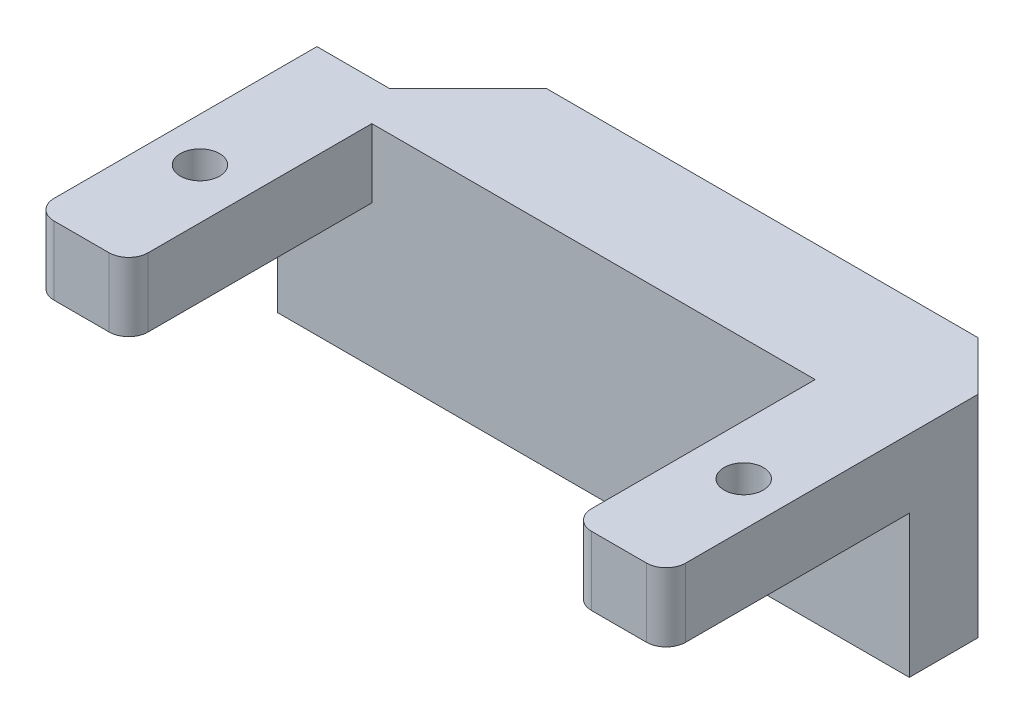
SolidWorks part; units mm, degrees
ref_plane "Front Plane" through (0, 0, 0) normal (0, 0, 1) x (1, 0, 0)
ref_plane "Top Plane" through (0, 0, 0) normal (0, 1, 0) x (1, 0, 0)
ref_plane "Right Plane" through (0, 0, 0) normal (1, 0, 0) x (0, 0, -1)
sketch "Sketch1" plane through (0, 0, 0) normal (0, 0, 1) x (1, 0, 0)
  line L1 (-16.1, 12.75) -> (16.1, 12.75)
  line L2 (-16.1, 12.75) -> (-16.1, -12.75)
  line L3 (-16.1, -12.75) -> (16.1, -12.75)
  line L4 (16.1, 12.75) -> (16.1, -12.75)
  line L5 (-16.1, 12.75) -> (16.1, -12.75) construction
  line L6 (-16.1, -12.75) -> (16.1, 12.75) construction
  point P0 (0, 0)
  dimension "D1" = 32.2
  dimension "D2" = 25.5
extrude "Boss-Extrude1" add sketch "Sketch1" along normal blind 14.4
sketch "Sketch3" plane through (0, 0, 14.4) normal (0, 0, 1) x (1, 0, 0)
  line L0 (-16.1, 12.75) -> (-16.1, -12.75) construction
  line L1 (-16.1, 10.75) -> (16.1, 10.75)
  line L2 (-16.1, 10.75) -> (-16.1, -11)
  line L3 (-16.1, -11) -> (16.1, -11)
  line L4 (16.1, 10.75) -> (16.1, -11)
  line L5 (16.1, -12.75) -> (16.1, 12.75) construction
  line L6 (16.1, 12.75) -> (-16.1, 12.75) construction
  dimension "D1" = 2
  dimension "D2" = 21.75
extrude "Cut-Extrude1" cut sketch "Sketch3" against normal blind 12.4
sketch "Sketch5" plane through (0, 0, 14.4) normal (0, 0, 1) x (1, 0, 0)
  line L0 (16.1, 12.75) -> (-16.1, 12.75) construction
  line L1 (-11.3, 12.75) -> (11.3, 12.75)
  line L2 (-11.3, 12.75) -> (-11.3, 10.75)
  line L3 (-11.3, 10.75) -> (11.3, 10.75)
  line L4 (11.3, 12.75) -> (11.3, 10.75)
  line L5 (16.1, 10.75) -> (-16.1, 10.75) construction
  line L6 (-16.1, 12.75) -> (-16.1, 10.75) construction
  line L7 (16.1, 10.75) -> (16.1, 12.75) construction
  dimension "D1" = 4.8
  dimension "D2" = 4.8
extrude "Cut-Extrude2" cut sketch "Sketch5" against normal blind 14.4 contours L2 L1 L4 L3
fillet "Fillet1" radius 1 1 edges at (-11.3, 11.75, 14.4)
fillet "Fillet2" radius 1 1 edges at (-16.1, 11.75, 14.4)
fillet "Fillet3" radius 1 1 edges at (11.3, 11.75, 14.4)
fillet "Fillet4" radius 1 1 edges at (16.1, 11.75, 14.4)
sketch "Sketch10" plane through (0, 12.75, 0) normal (0, 1, 0) x (1, 0, 0)
  line L0 (-16.1, -13.4) -> (-16.1, 0) construction
  circle A0 centre (-13.86, -8.203) radius 1
  dimension "D1" = 2.24
extrude "Cut-Extrude3" cut sketch "Sketch10" against normal blind 10
mirror "Mirror1" about plane through (0, 0, 0) normal (1, 0, 0) of "Cut-Extrude3"
sketch "Sketch11" plane through (0, 0, 14.4) normal (0, 0, 1) x (1, 0, 0)
  line L0 (-16.1, -12.75) -> (16.1, -12.75) construction
  line L1 (-16.1, -11) -> (-11.25, -11)
  line L2 (-16.1, -11) -> (-16.1, -12.75)
  line L3 (-16.1, -12.75) -> (-11.25, -12.75)
  line L4 (-11.25, -11) -> (-11.25, -12.75)
  dimension "D1" = 4.85
extrude "Cut-Extrude4" cut sketch "Sketch11" against normal blind 20
mirror "Mirror2" about plane through (0, 0, 0) normal (1, 0, 0) of "Cut-Extrude4"
fillet "Fillet5" radius 1 6 edges at (-11.25, -11.875, 0) (-16.1, -11, 1) (16.1, -11, 1) (11.25, -11.875, 0) (11.25, -11.875, 14.4) (-11.25, -11.875, 14.4)
sketch "Sketch12" plane through (0, 0, 0) normal (0, 0, -1) x (-1, 0, 0)
  line L1 (-12.6, 5.5) -> (7.4, 5.5)
  line L2 (-12.6, 5.5) -> (-12.6, 3.5)
  line L3 (-12.6, 3.5) -> (7.4, 3.5)
  line L4 (7.4, 5.5) -> (7.4, 3.5)
  line L6 (11.3, 10.75) -> (-11.3, 10.75) construction
  line L9 (-16.1, -10) -> (-16.1, 12.75) construction
  dimension "D1" = 5.25
  dimension "D2" = 2
  dimension "D3" = 20
  dimension "D4" = 3.5
extrude "Boss-Extrude2" add sketch "Sketch12" along normal blind 5
sketch "Sketch13" plane through (0, 0, 0) normal (0, 0, -1) x (-1, 0, 0)
  line L0 (7.4, 5.5) -> (-12.6, 5.5) construction
  line L1 (-12.6, 9) -> (7.4, 9)
  line L2 (-12.6, 9) -> (-12.6, 7)
  line L3 (-11.6, 7) -> (6.4, 7)
  line L4 (7.4, 9) -> (7.4, 7)
  line L5 (-2.6, 7) -> (-2.6, 5.5) construction
  line L7 (-12.6, 7) -> (-12.6, 5.5)
  line L8 (-12.6, 5.5) -> (-11.6, 5.5)
  line L9 (-11.6, 7) -> (-11.6, 5.5)
  line L10 (7.4, 5.5) -> (-12.6, 5.5) construction
  line L11 (7.4, 5.5) -> (6.4, 5.5)
  line L12 (6.4, 7) -> (6.4, 5.5)
  line L14 (7.4, 7) -> (7.4, 5.5)
  dimension "D1" = 1.5
  dimension "D2" = 1
extrude "Boss-Extrude3" add sketch "Sketch13" along normal blind 5
sketch "Sketch14" plane through (0, 3.5, 0) normal (0, -1, 0) x (1, 0, 0)
  line L1 (-19.2363, 15.8932) -> (18.6063, 15.8932)
  line L2 (-19.2363, 15.8932) -> (-19.2363, -6.2412)
  line L3 (-19.2363, -6.2412) -> (18.6063, -6.2412)
  line L4 (18.6063, 15.8932) -> (18.6063, -6.2412)
extrude "Cut-Extrude5" cut sketch "Sketch14" along normal through all
sketch "Sketch15" plane through (0, 12.75, 0) normal (0, 1, 0) x (1, 0, 0)
  line L0 (-7.4, 0) -> (12.6, 0) construction
  line L1 (12.6, 0) -> (12.6, 5) construction
  line L2 (12.6, 5) -> (-7.4, 5) construction
  line L3 (-7.4, 5) -> (-7.4, 0) construction
  line L4 (-11.3, -2) -> (11.3, -2) construction
  line L5 (11.3, -2) -> (11.3, 0) construction
  line L6 (11.3, 0) -> (-11.3, 0) construction
  line L7 (-11.3, 0) -> (-11.3, -2) construction
  line L8 (11.3, 0) -> (12.6, 0)
  line L9 (12.6, 0) -> (12.6, 5)
  line L10 (12.6, 5) -> (-7.4, 5)
  line L11 (-7.4, 5) -> (-7.4, 0)
  line L12 (-11.3, -2) -> (11.3, -2)
  line L13 (11.3, -2) -> (11.3, 0)
  line L14 (-7.4, 0) -> (-11.3, 0)
  line L15 (-11.3, 0) -> (-11.3, -2)
extrude "Boss-Extrude5" add sketch "Sketch15" against normal up to surface (3.75 mm away) up to face at (2.6, 9, -2.5)
chamfer "Chamfer1" distance 5 angle 45 2 edges at (-7.4, 8.125, 0) (12.6, 8.125, 0)
sketch "Sketch16" plane through (0, 12.75, 0) normal (0, 1, 0) x (1, 0, 0)
  line L11 (16.1, -13.4) -> (16.1, 1.5)
  line L12 (16.1, 1.5) -> (12.6, 5)
  line L13 (12.6, 5) -> (-7.4, 5)
  line L14 (-7.4, 5) -> (-12.4, 0)
  line L15 (-12.4, 0) -> (-16.1, 0)
  line L16 (-16.1, 0) -> (-16.1, -13.4)
  line L17 (-15.1, -14.4) -> (-12.3, -14.4)
  line L18 (-11.3, -13.4) -> (-11.3, -2)
  line L19 (-11.3, -2) -> (11.3, -2)
  line L20 (11.3, -2) -> (11.3, -13.4)
  line L21 (12.3, -14.4) -> (15.1, -14.4)
  line L22 (16.1, -13.4) -> (16.1, 1.5)
  line L23 (16.1, 1.5) -> (12.6, 5)
  line L24 (12.6, 5) -> (-7.4, 5)
  line L25 (-7.4, 5) -> (-12.4, 0)
  line L26 (-12.4, 0) -> (-16.1, 0)
  line L27 (-16.1, 0) -> (-16.1, -13.4)
  line L28 (-15.1, -14.4) -> (-12.3, -14.4)
  line L29 (-11.3, -13.4) -> (-11.3, -2)
  line L30 (-11.3, -2) -> (11.3, -2)
  line L31 (11.3, -2) -> (11.3, -13.4)
  line L32 (12.3, -14.4) -> (15.1, -14.4)
  circle A0 centre (13.86, -8.203) radius 1 construction
  circle A1 centre (-13.86, -8.203) radius 1 construction
  circle A2 centre (13.86, -8.203) radius 1
  circle A3 centre (-13.86, -8.203) radius 1
  arc A4 (-16.1, -13.4) -> (-15.1, -14.4) centre (-15.1, -13.4) ccw
  arc A5 (-12.3, -14.4) -> (-11.3, -13.4) centre (-12.3, -13.4) ccw
  arc A6 (11.3, -13.4) -> (12.3, -14.4) centre (12.3, -13.4) ccw
  arc A7 (15.1, -14.4) -> (16.1, -13.4) centre (15.1, -13.4) ccw
  arc A8 (-16.1, -13.4) -> (-15.1, -14.4) centre (-15.1, -13.4) ccw
  arc A9 (-12.3, -14.4) -> (-11.3, -13.4) centre (-12.3, -13.4) ccw
  arc A10 (11.3, -13.4) -> (12.3, -14.4) centre (12.3, -13.4) ccw
  arc A11 (15.1, -14.4) -> (16.1, -13.4) centre (15.1, -13.4) ccw
  dimension "D1" = 0
extrude "Boss-Extrude6" add sketch "Sketch16" along normal blind 1.5
sketch "Sketch17" plane through (0, 0, -5) normal (0, 0, -1) x (-1, 0, 0)
  line L1 (-18.3963, 20.4042) -> (13.5242, 20.4042)
  line L2 (-18.3963, 20.4042) -> (-18.3963, -1.8562)
  line L3 (-18.3963, -1.8562) -> (13.5242, -1.8562)
  line L4 (13.5242, 20.4042) -> (13.5242, -1.8562)
extrude "Cut-Extrude6" cut sketch "Sketch17" against normal blind 1
